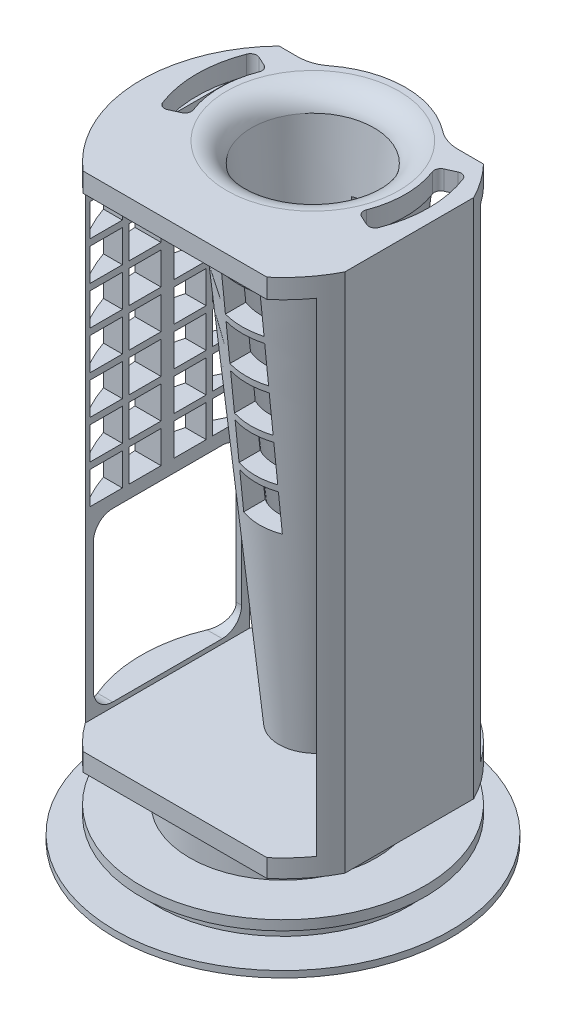
SolidWorks part; units mm, degrees
other "Детальный элемент1"
material "PP Кополимер"
ref_plane "Front Plane" through (0, 0, 0) normal (0, 0, 1) x (1, 0, 0)
ref_plane "Top Plane" through (0, 0, 0) normal (0, 1, 0) x (1, 0, 0)
ref_plane "Right Plane" through (0, 0, 0) normal (1, 0, 0) x (0, 0, -1)
sketch "Эскиз1" plane through (0, 0, 0) normal (0, 1, 0) x (1, 0, 0)
  line L0 (19.6, 9.992) -> (19.6, -9.992)
  line L1 (-14.2632, -16.75) -> (14.2632, -16.75)
  line L2 (-15.8568, 15.25) -> (-12.9239, 15.25)
  line L3 (11.9239, 15.25) -> (15.8568, 15.25)
  line L4 (-0.5, 5.125) -> (-0.5, 23.5612) construction
  line L5 (-0.5, 5.125) -> (-16.8682, 12.625) construction
  line L6 (-14.4479, 11.516) -> (-15.9323, 12.1962)
  line L7 (-14.4479, -1.266) -> (-15.9323, -1.9462)
  line L8 (-0.5, 5.125) -> (-16.8682, -2.375) construction
  line L9 (13.4479, 11.516) -> (14.9323, 12.1962)
  line L10 (13.4479, -1.266) -> (14.9323, -1.9462)
  arc A0 (19.6, 9.992) -> (15.8568, 15.25) centre (0, 0) ccw
  circle A1 centre (-0.5, 5.125) radius 9.5
  arc A2 (8.3046, 16.4881) -> (-9.3046, 16.4881) centre (-0.5, 5.125) ccw
  arc A3 (14.2632, -16.75) -> (19.6, -9.992) centre (0, 0) ccw
  arc A4 (-15.8568, 15.25) -> (-14.2632, -16.75) centre (0, 0) ccw
  arc A5 (-12.9239, 15.25) -> (-9.3046, 16.4881) centre (-12.9239, 21.1592) ccw
  arc A6 (11.9239, 15.25) -> (8.3046, 16.4881) centre (11.9239, 21.1592) cw
  arc A7 (8.3046, 16.4881) -> (-9.3046, 16.4881) centre (-0.5, 5.125) ccw
  arc A9 (-13.9302, 10.2504) -> (-13.9302, -0.0004) centre (-0.5, 5.125) ccw
  arc A10 (-17.2809, 11.6494) -> (-17.2809, -1.3994) centre (-0.5, 5.125) ccw
  arc A11 (-15.9323, -1.9462) -> (-17.2809, -1.3994) centre (-16.3489, -1.0371) cw
  arc A12 (-13.9302, -0.0004) -> (-14.4479, -1.266) centre (-14.8645, -0.3569) cw
  arc A13 (-14.4479, 11.516) -> (-13.9302, 10.2504) centre (-14.8645, 10.6069) cw
  arc A14 (-17.2809, 11.6494) -> (-15.9323, 12.1962) centre (-16.3489, 11.2871) cw
  arc A15 (13.4479, 11.516) -> (12.9302, 10.2504) centre (13.8645, 10.6069) ccw
  arc A16 (16.2809, 11.6494) -> (14.9323, 12.1962) centre (15.3489, 11.2871) ccw
  arc A17 (12.9302, -0.0004) -> (13.4479, -1.266) centre (13.8645, -0.3569) ccw
  arc A18 (14.9323, -1.9462) -> (16.2809, -1.3994) centre (15.3489, -1.0371) ccw
  arc A19 (12.9302, 10.2504) -> (12.9302, -0.0004) centre (-0.5, 5.125) cw
  arc A20 (16.2809, 11.6494) -> (16.2809, -1.3994) centre (-0.5, 5.125) cw
  point P6 (-18.5046, 5.125)
  point P19 (-13.2574, -1.4999)
  point P28 (-13.5684, -0.863)
  point P31 (-13.5684, 11.113)
  dimension "D1" = 44
  dimension "D3" = 19
  dimension "D5" = 28.75
  dimension "D9" = 15
  dimension "D10" = 1
  dimension "D2" = 41.6
  dimension "D4" = 10.6
  dimension "D6" = 38.75
  dimension "D7" = 36.25
  dimension "D8" = 32
extrude "основание" add sketch "Эскиз1" along normal blind 3 contours L3 A6 A2 A5 L2 A4 L1 A3 L0 A0 A1 A10 A14 L6 A13 A9 A12 L7 A11 A16 A20 A18 L10 A17 A19 A15 L9 region at (19.0482, 0, 0)
sketch "Эскиз2" plane through (0, 0, 0) normal (0, 1, 0) x (1, 0, 0)
  line L0 (19.6, 9.992) -> (19.6, -9.992) construction
  line L1 (-17.9223, -12.759) -> (17.9223, -12.759) construction
  line L2 (-17.9223, -12.759) -> (-17.9223, 12.759)
  line L3 (-17.9223, 12.759) -> (17.9223, 12.759) construction
  line L4 (17.9223, -12.759) -> (17.9223, 12.759)
  line L5 (-17.9223, -12.759) -> (17.9223, 12.759) construction
  line L6 (-17.9223, 12.759) -> (17.9223, -12.759) construction
  line L7 (19.6, 9.992) -> (19.6, -9.992)
  arc A0 (19.6, 9.992) -> (15.8568, 15.25) centre (0, 0) ccw construction
  arc A1 (-15.8568, 15.25) -> (-14.2632, -16.75) centre (0, 0) ccw construction
  arc A2 (-17.9223, 12.759) -> (-17.9223, -12.759) centre (0, 0) ccw
  arc A3 (14.2632, -16.75) -> (19.6, -9.992) centre (0, 0) ccw construction
  arc A4 (17.9223, -12.759) -> (19.6, -9.992) centre (0, 0) ccw
  arc A5 (19.6, 9.992) -> (17.9223, 12.759) centre (0, 0) ccw
  point P0 (0, 0)
  dimension "D1" = 35.8445
extrude "боковые ребра" add sketch "Эскиз2" against normal blind 75
sketch "Эскиз3" plane through (0, -75, 0) normal (0, -1, 0) x (-1, 0, 0)
  line L0 (14.2632, -16.75) -> (-14.2632, -16.75)
  line L1 (14.2632, -16.75) -> (-14.2632, -16.75) construction
  line L3 (15.8568, 15.25) -> (-7.5223, 20.674)
  line L4 (-19.6, 9.992) -> (-19.6, -9.992)
  line L5 (-19.6, -9.992) -> (-19.6, 9.992) construction
  arc A0 (-7.5223, 20.674) -> (-19.6, 9.992) centre (0, 0) ccw
  arc A1 (-14.2632, -16.75) -> (15.8568, 15.25) centre (0, 0) ccw
  arc A5 (-19.6, -9.992) -> (-14.2632, -16.75) centre (0, 0) ccw
  arc M2 (17.9223, -12.759) -> (17.9223, 12.759) centre (0, 0) ccw
  line M3 (17.9223, 12.759) -> (17.9223, -12.759)
  dimension "D1" = 24
extrude "примыкание ручки" add sketch "Эскиз3" along normal blind 2.8 contours L0 A1 L3 A0 M3 | M3 M2 region at (0.7797, -75, -0.6462) region at (-19.5671, -75, 0)
sketch "Эскиз4" plane through (-17.9223, 0, 0) normal (1, 0, 0) x (0, 0, -1)
  line L0 (0, 0) -> (0, -77.8) construction
  line L1 (9.992, -77.8) -> (-9.992, -77.8) construction
  line L2 (-16.75, -77.8) -> (15.25, -77.8) construction
  line L3 (8.5, -74.3) -> (-8.5, -74.3)
  line L4 (11.5, -71.3) -> (11.5, -51.3)
  line L5 (8.5, -48.3) -> (-8.5, -48.3)
  line L6 (-11.5, -71.3) -> (-11.5, -51.3)
  line L7 (11.5, -74.3) -> (-11.5, -48.3) construction
  line L8 (11.5, -48.3) -> (-11.5, -74.3) construction
  line L9 (12, -41.3) -> (12, -46.3)
  line L10 (6, -41.3) -> (1, -41.3)
  line L11 (6, -41.3) -> (6, -46.3)
  line L12 (6, -46.3) -> (1, -46.3)
  line L13 (1, -41.3) -> (1, -46.3)
  line L14 (6, -41.3) -> (1, -46.3) construction
  line L15 (6, -46.3) -> (1, -41.3) construction
  line L16 (12, -41.3) -> (7, -41.3)
  line L17 (7, -41.3) -> (7, -46.3)
  line L18 (12, -46.3) -> (7, -46.3)
  line L19 (-6, -46.3) -> (-1, -46.3)
  line L20 (-12, -46.3) -> (-7, -46.3)
  line L21 (-6, -46.3) -> (-1, -41.3) construction
  line L22 (-6, -41.3) -> (-1, -46.3) construction
  line L23 (-7, -41.3) -> (-7, -46.3)
  line L24 (-12, -41.3) -> (-7, -41.3)
  line L25 (-1, -41.3) -> (-1, -46.3)
  line L26 (-6, -41.3) -> (-6, -46.3)
  line L27 (-6, -41.3) -> (-1, -41.3)
  line L28 (-12, -41.3) -> (-12, -46.3)
  line L29 (12, -35.3) -> (12, -40.3)
  line L30 (6, -35.3) -> (1, -35.3)
  line L31 (6, -35.3) -> (6, -40.3)
  line L32 (6, -40.3) -> (1, -40.3)
  line L33 (1, -35.3) -> (1, -40.3)
  line L34 (12, -35.3) -> (7, -35.3)
  line L35 (7, -35.3) -> (7, -40.3)
  line L36 (12, -40.3) -> (7, -40.3)
  line L37 (-6, -40.3) -> (-1, -40.3)
  line L38 (-12, -40.3) -> (-7, -40.3)
  line L39 (-7, -35.3) -> (-7, -40.3)
  line L40 (-12, -35.3) -> (-7, -35.3)
  line L41 (-1, -35.3) -> (-1, -40.3)
  line L42 (-6, -35.3) -> (-6, -40.3)
  line L43 (-6, -35.3) -> (-1, -35.3)
  line L44 (-12, -35.3) -> (-12, -40.3)
  line L45 (6, -35.3) -> (1, -40.3) construction
  line L46 (6, -40.3) -> (1, -35.3) construction
  line L47 (-6, -40.3) -> (-1, -35.3) construction
  line L48 (-6, -35.3) -> (-1, -40.3) construction
  line L49 (12, -29.3) -> (12, -34.3)
  line L50 (6, -29.3) -> (1, -29.3)
  line L51 (6, -29.3) -> (6, -34.3)
  line L52 (6, -34.3) -> (1, -34.3)
  line L53 (1, -29.3) -> (1, -34.3)
  line L54 (12, -29.3) -> (7, -29.3)
  line L55 (7, -29.3) -> (7, -34.3)
  line L56 (12, -34.3) -> (7, -34.3)
  line L57 (-6, -34.3) -> (-1, -34.3)
  line L58 (-12, -34.3) -> (-7, -34.3)
  line L59 (-7, -29.3) -> (-7, -34.3)
  line L60 (-12, -29.3) -> (-7, -29.3)
  line L61 (-1, -29.3) -> (-1, -34.3)
  line L62 (-6, -29.3) -> (-6, -34.3)
  line L63 (-6, -29.3) -> (-1, -29.3)
  line L64 (-12, -29.3) -> (-12, -34.3)
  line L65 (6, -29.3) -> (1, -34.3) construction
  line L66 (6, -34.3) -> (1, -29.3) construction
  line L67 (-6, -34.3) -> (-1, -29.3) construction
  line L68 (-6, -29.3) -> (-1, -34.3) construction
  line L69 (12, -23.3) -> (12, -28.3)
  line L70 (6, -23.3) -> (1, -23.3)
  line L71 (6, -23.3) -> (6, -28.3)
  line L72 (6, -28.3) -> (1, -28.3)
  line L73 (1, -23.3) -> (1, -28.3)
  line L74 (12, -23.3) -> (7, -23.3)
  line L75 (7, -23.3) -> (7, -28.3)
  line L76 (12, -28.3) -> (7, -28.3)
  line L77 (-6, -28.3) -> (-1, -28.3)
  line L78 (-12, -28.3) -> (-7, -28.3)
  line L79 (-7, -23.3) -> (-7, -28.3)
  line L80 (-12, -23.3) -> (-7, -23.3)
  line L81 (-1, -23.3) -> (-1, -28.3)
  line L82 (-6, -23.3) -> (-6, -28.3)
  line L83 (-6, -23.3) -> (-1, -23.3)
  line L84 (-12, -23.3) -> (-12, -28.3)
  line L85 (6, -23.3) -> (1, -28.3) construction
  line L86 (6, -28.3) -> (1, -23.3) construction
  line L87 (-6, -28.3) -> (-1, -23.3) construction
  line L88 (-6, -23.3) -> (-1, -28.3) construction
  line L89 (12, -17.3) -> (12, -22.3)
  line L90 (6, -17.3) -> (1, -17.3)
  line L91 (6, -17.3) -> (6, -22.3)
  line L92 (6, -22.3) -> (1, -22.3)
  line L93 (1, -17.3) -> (1, -22.3)
  line L94 (12, -17.3) -> (7, -17.3)
  line L95 (7, -17.3) -> (7, -22.3)
  line L96 (12, -22.3) -> (7, -22.3)
  line L97 (-6, -22.3) -> (-1, -22.3)
  line L98 (-12, -22.3) -> (-7, -22.3)
  line L99 (-7, -17.3) -> (-7, -22.3)
  line L100 (-12, -17.3) -> (-7, -17.3)
  line L101 (-1, -17.3) -> (-1, -22.3)
  line L102 (-6, -17.3) -> (-6, -22.3)
  line L103 (-6, -17.3) -> (-1, -17.3)
  line L104 (-12, -17.3) -> (-12, -22.3)
  line L105 (6, -17.3) -> (1, -22.3) construction
  line L106 (6, -22.3) -> (1, -17.3) construction
  line L107 (-6, -22.3) -> (-1, -17.3) construction
  line L108 (-6, -17.3) -> (-1, -22.3) construction
  line L109 (12, -11.3) -> (12, -16.3)
  line L110 (6, -11.3) -> (1, -11.3)
  line L111 (6, -11.3) -> (6, -16.3)
  line L112 (6, -16.3) -> (1, -16.3)
  line L113 (1, -11.3) -> (1, -16.3)
  line L114 (12, -11.3) -> (7, -11.3)
  line L115 (7, -11.3) -> (7, -16.3)
  line L116 (12, -16.3) -> (7, -16.3)
  line L117 (-6, -16.3) -> (-1, -16.3)
  line L118 (-12, -16.3) -> (-7, -16.3)
  line L119 (-7, -11.3) -> (-7, -16.3)
  line L120 (-12, -11.3) -> (-7, -11.3)
  line L121 (-1, -11.3) -> (-1, -16.3)
  line L122 (-6, -11.3) -> (-6, -16.3)
  line L123 (-6, -11.3) -> (-1, -11.3)
  line L124 (-12, -11.3) -> (-12, -16.3)
  line L125 (6, -11.3) -> (1, -16.3) construction
  line L126 (6, -16.3) -> (1, -11.3) construction
  line L127 (-6, -16.3) -> (-1, -11.3) construction
  line L128 (-6, -11.3) -> (-1, -16.3) construction
  line L129 (12, -5.3) -> (12, -10.3)
  line L130 (6, -5.3) -> (1, -5.3)
  line L131 (6, -5.3) -> (6, -10.3)
  line L132 (6, -10.3) -> (1, -10.3)
  line L133 (1, -5.3) -> (1, -10.3)
  line L134 (12, -5.3) -> (7, -5.3)
  line L135 (7, -5.3) -> (7, -10.3)
  line L136 (12, -10.3) -> (7, -10.3)
  line L137 (-6, -10.3) -> (-1, -10.3)
  line L138 (-12, -10.3) -> (-7, -10.3)
  line L139 (-7, -5.3) -> (-7, -10.3)
  line L140 (-12, -5.3) -> (-7, -5.3)
  line L141 (-1, -5.3) -> (-1, -10.3)
  line L142 (-6, -5.3) -> (-6, -10.3)
  line L143 (-6, -5.3) -> (-1, -5.3)
  line L144 (-12, -5.3) -> (-12, -10.3)
  line L145 (6, -5.3) -> (1, -10.3) construction
  line L146 (6, -10.3) -> (1, -5.3) construction
  line L147 (-6, -10.3) -> (-1, -5.3) construction
  line L148 (-6, -5.3) -> (-1, -10.3) construction
  arc A0 (8.5, -74.3) -> (11.5, -71.3) centre (8.5, -71.3) ccw
  arc A1 (-8.5, -74.3) -> (-11.5, -71.3) centre (-8.5, -71.3) cw
  arc A2 (-8.5, -48.3) -> (-11.5, -51.3) centre (-8.5, -51.3) ccw
  arc A3 (11.5, -51.3) -> (8.5, -48.3) centre (8.5, -51.3) ccw
  point P5 (0, -61.3)
  point P24 (3.5, -43.8)
  point P29 (1, -43.8)
  point P42 (-3.5, -43.8)
  point P44 (3.5, -37.8)
  point P62 (-3.5, -37.8)
  point P63 (3.5, -31.8)
  point P80 (-3.5, -31.8)
  point P81 (3.5, -25.8)
  point P98 (-3.5, -25.8)
  point P99 (3.5, -19.8)
  point P116 (-3.5, -19.8)
  point P117 (3.5, -13.8)
  point P134 (-3.5, -13.8)
  point P135 (3.5, -7.8)
  point P152 (-3.5, -7.8)
  dimension "D4" = 3
  dimension "D1" = 23
  dimension "D2" = 26
  dimension "D3" = 3.5
  dimension "D5" = 5
  dimension "D6" = 2
  dimension "D7" = 2
  dimension "D8" = 2
  dimension "D9" = 7
extrude "перфорация боковых стенок" cut sketch "Эскиз4" against normal through all
sketch "Эскиз6" plane through (0, 0, 0) normal (0, -1, 0) x (-1, 0, 0)
  point P0 (0.5, 5.125)
ref_plane "Плоскость1" through (0, 0, -5.125) normal (0, 0, -1) x (-1, 0, 0)
sketch "Эскиз7" plane through (0, 0, -5.125) normal (0, 0, -1) x (-1, 0, 0)
  line L0 (0, 0) -> (0, -75) construction
  line L1 (15.8568, -75) -> (-7.5223, -75) construction
  line L2 (2.736, -75) -> (10, 0)
  line L3 (-8.3046, 0) -> (9.3046, 0) construction
  line L4 (10, 0) -> (13.014, 0)
  line L6 (13.014, 0) -> (5.75, -75)
  line L7 (5.75, -75) -> (2.736, -75)
  line L9 (-9, 0) -> (10, 0) construction
  point P10 (10, 0)
  point P12 (8.1066, 0)
  point P14 (11.1142, 0)
  point P15 (0, 0)
  dimension "D1" = 11.5
  dimension "D2" = 3
revolve "внутрении конус" add sketch "Эскиз7" angle 360 about L0
sketch "Эскиз8" plane through (0, 0, -5.125) normal (0, 0, -1) x (-1, 0, 0)
  line L0 (0, 0) -> (0, -75) construction
  line L1 (15.8568, -75) -> (-7.5223, -75) construction
  line L2 (-8.3046, 0) -> (9.3046, 0) construction
  line L3 (-3, -10) -> (3, -10)
  line L4 (-3, -10) -> (-3, -16)
  line L5 (-3, -16) -> (3, -16)
  line L6 (3, -10) -> (3, -16)
  line L7 (-3, -10) -> (3, -16) construction
  line L8 (-3, -16) -> (3, -10) construction
  line L9 (-3, -17) -> (-3, -23)
  line L10 (-3, -17) -> (3, -17)
  line L11 (-3, -23) -> (3, -23)
  line L12 (3, -17) -> (3, -23)
  line L13 (-3, -24) -> (-3, -30)
  line L14 (-3, -24) -> (3, -24)
  line L15 (-3, -30) -> (3, -30)
  line L16 (3, -24) -> (3, -30)
  line L17 (-3, -31) -> (-3, -37)
  line L18 (-3, -31) -> (3, -31)
  line L19 (-3, -37) -> (3, -37)
  line L20 (3, -31) -> (3, -37)
  line L21 (-3, -38) -> (-3, -44)
  line L22 (-3, -38) -> (3, -38)
  line L23 (-3, -44) -> (3, -44)
  line L24 (3, -38) -> (3, -44)
  point P5 (0, -13)
  dimension "D1" = 6
  dimension "D2" = 10
  dimension "D3" = 5
extrude "перфорация конуса" cut sketch "Эскиз8" against normal through all both and the other way through all
fillet "Скруг основ конуса" radius 4 1 edges at (-0.5, 3, 4.375)
sketch "Эскиз9" plane through (0, -77.8, 0) normal (0, -1, 0) x (1, 0, 0)
  circle A0 centre (0, 0) radius 14.4801
extrude "шейка ручки" add sketch "Эскиз9" along normal blind 5.5
sketch "Эскиз10" plane through (0, -83.3, 0) normal (0, -1, 0) x (1, 0, 0)
  circle A0 centre (0, 0) radius 22
  dimension "D1" = 44
extrude "бортик перед прокладкой" add sketch "Эскиз10" along normal blind 1.5
sketch "Эскиз11" plane through (0, -84.8, 0) normal (0, -1, 0) x (1, 0, 0)
  circle A0 centre (0, 0) radius 19.5
  dimension "D1" = 39
extrude "прокладка паз" add sketch "Эскиз11" along normal blind 2.5
sketch "Эскиз12" plane through (0, -87.3, 0) normal (0, -1, 0) x (-1, 0, 0)
  circle A0 centre (0, 0) radius 26
  dimension "D1" = 52
extrude "бортик после прокладки" add sketch "Эскиз12" along normal blind 1
sketch "Эскиз13" plane through (0, -88.3, 0) normal (0, -1, 0) x (1, 0, 0)
  circle A0 centre (0, 0) radius 12
extrude "вырез под внеш ручку" cut sketch "Эскиз13" against normal blind 11
chamfer "фаска под ручку " distance 8 distance2 5 1 edges at (0, -88.3, -12) first distance on face at (0, -88.3, -12)
sketch "Эскиз14" plane through (0, -77.3, 0) normal (0, -1, 0) x (1, 0, 0)
  line L0 (0, 0) -> (-8, 9.6047) construction
  line L1 (0, 0) -> (8, 9.6047) construction
  line L2 (-8, 9.6047) -> (-7.36, 8.8363)
  line L3 (8, 9.6047) -> (7.36, 8.8363)
  line L4 (0, 0) -> (0, 16.9399) construction
  line L5 (9.6047, 8) -> (8.8363, 7.36)
  line L6 (9.6047, -8) -> (8.8363, -7.36)
  line L7 (8, -9.6047) -> (7.36, -8.8363)
  line L8 (-8, -9.6047) -> (-7.36, -8.8363)
  line L9 (-9.6047, -8) -> (-8.8363, -7.36)
  line L10 (-9.6047, 8) -> (-8.8363, 7.36)
  arc A0 (7.36, 8.8363) -> (-7.36, 8.8363) centre (0, 0) ccw
  arc A1 (8, 9.6047) -> (-8, 9.6047) centre (0, 0) ccw
  arc A2 (8.8363, -7.36) -> (8.8363, 7.36) centre (0, 0) ccw
  arc A3 (9.6047, -8) -> (9.6047, 8) centre (0, 0) ccw
  arc A4 (-7.36, -8.8363) -> (7.36, -8.8363) centre (0, 0) ccw
  arc A5 (-8, -9.6047) -> (8, -9.6047) centre (0, 0) ccw
  arc A6 (-8.8363, 7.36) -> (-8.8363, -7.36) centre (0, 0) ccw
  arc A7 (-9.6047, 8) -> (-9.6047, -8) centre (0, 0) ccw
  point P22 (0, 0)
  dimension "D1" = 23
  dimension "D2" = 16
  dimension "D3" = 25
  dimension "D4" = 4
extrude "защелки для ручки" add sketch "Эскиз14" along normal blind 3 from offset 5
chamfer "Фаска2" distance 2 distance2 0.8 4 edges at (0, -85.3, -11.5) (11.5, -85.3, 0) (0, -85.3, 11.5) (-11.5, -85.3, 0) first distance on face at (0, -83.8, -10.1682) first distance on face at (10.1682, -83.8, 0) first distance on face at (0, -83.8, 10.1682) first distance on face at (-10.1682, -83.8, 0)
